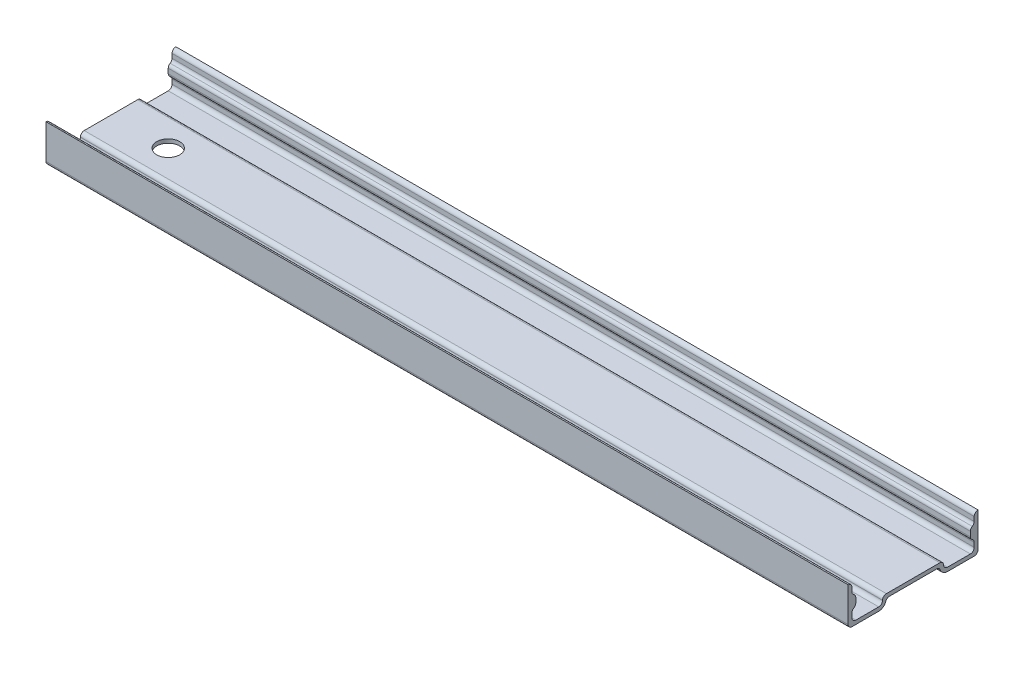
SolidWorks part; units mm, degrees
ref_plane "Front Plane" through (0, 0, 0) normal (0, 0, 1) x (1, 0, 0)
ref_plane "Top Plane" through (0, 0, 0) normal (0, 1, 0) x (1, 0, 0)
ref_plane "Right Plane" through (0, 0, 0) normal (1, 0, 0) x (0, 0, -1)
sketch "Sketch1" plane through (0, 0, 0) normal (0, 1, 0) x (1, 0, 0)
  line L0 (-105, 17) -> (105, -17) construction
  line L1 (-105, 17) -> (105, 17)
  line L2 (-105, 17) -> (-105, -17)
  line L3 (-105, -17) -> (105, -17)
  line L4 (105, 17) -> (105, -17)
  dimension "D1" = 34
  dimension "D2" = 210
extrude "Boss-Extrude1" add sketch "Sketch1" along normal blind 1
sketch "Sketch2" plane through (0, 1, 0) normal (0, 1, 0) x (1, 0, 0)
  line L0 (105, -17) -> (105, 17) construction
  line L1 (-105, 17) -> (105, 17)
  line L2 (-105, 17) -> (-105, 16)
  line L3 (-105, 16) -> (105, 16)
  line L4 (105, 17) -> (105, 16)
  line L6 (105, -16) -> (-105, -16)
  line L7 (105, -16) -> (105, -17)
  line L8 (105, -17) -> (-105, -17)
  line L9 (-105, -16) -> (-105, -17)
  dimension "D1" = 1
  dimension "D2" = 1
extrude "Boss-Extrude2" add sketch "Sketch2" along normal blind 9
sketch "Sketch3" plane through (0, 1, 0) normal (0, 1, 0) x (1, 0, 0)
  line L0 (-105, 16) -> (-105, -16) construction
  line L1 (-105, 8) -> (105, 8)
  line L2 (-105, 8) -> (-105, -8)
  line L3 (-105, -8) -> (105, -8)
  line L4 (105, 8) -> (105, -8)
  line L5 (105, -16) -> (105, 16) construction
  line L6 (-105, 8) -> (105, -8) construction
  dimension "D1" = 16
extrude "Boss-Extrude3" add sketch "Sketch3" along normal blind 2
fillet "Fillet1" radius 1 1 edges at (0, 1, 8) type face fillet first side face at (0, 2, 8) second side face at (0, 1, 12)
fillet "Fillet2" radius 1 1 edges at (0, 1, -8) type face fillet first side face at (0, 2, -8) second side face at (-26.25, 1, -12)
fillet "Fillet3" radius 1 1 edges at (0, 1, 16) type face fillet first side face at (0, 1, 12.5) second side face at (0, 5.5, 16)
fillet "Fillet4" radius 1 1 edges type face fillet first side face at (-26.25, 7.75, -16) second side face at (-26.25, 1, -12.5)
fillet "Fillet5" radius 1 1 edges at (0, 10, -16) type face fillet first side face at (0, 8, -16) second side face at (0, 10, -16.5)
fillet "Fillet6" radius 1 1 edges at (0, 10, 16) type face fillet first side face at (0, 6, 16) second side face at (0, 10, 16.5)
sketch "Sketch4" plane through (105, 0, 0) normal (1, 0, 0) x (0, 0, -1)
  line L0 (-9, 0) -> (9, 0)
  line L4 (-6.1716, 2) -> (6.1716, 2)
  arc A0 (-6.1716, 2) -> (-7.1144, 1.3333) centre (-6.1716, 1) ccw
  arc A1 (7.1144, 1.3333) -> (6.1716, 2) centre (6.1716, 1) ccw
  arc A2 (9, 0) -> (7.1144, 1.3333) centre (9, 2) cw
  arc A3 (-7.1144, 1.3333) -> (-9, 0) centre (-9, 2) cw
  dimension "D1" = 1
  dimension "D2" = 1
extrude "Cut-Extrude1" cut sketch "Sketch4" against normal through all
fillet "Fillet7" radius 1 1 edges at (0, 3, 8) type face fillet first side face at (0, 3, 0) second side face at (0, 2.5, 8)
fillet "Fillet8" radius 1 1 edges at (0, 3, -8) type face fillet first side face at (0, 3, -0.5) second side face at (0, 2.5, -8)
fillet "Fillet9" radius 1 1 edges at (0, 0, -17) type face fillet first side face at (0, 5, -17) second side face at (0, 0, -13)
fillet "Fillet10" radius 1 1 edges at (0, 0, 17) type face fillet first side face at (0, 5, 17) second side face at (0, 0, 13)
sketch "Sketch5" plane through (105, 0, 0) normal (1, 0, 0) x (0, 0, -1)
  line L0 (-15, 6.8718) -> (15, 6.8718) construction
  line L1 (-18, 6.8718) -> (-15, 6.8718)
  line L2 (-18, 6.8718) -> (-18, 3.8718)
  line L3 (-18, 3.8718) -> (-15, 3.8718)
  line L4 (-15, 6.8718) -> (-15, 3.8718)
  line L5 (15, 6.8718) -> (18, 6.8718)
  line L6 (15, 6.8718) -> (15, 3.8718)
  line L7 (15, 3.8718) -> (18, 3.8718)
  line L8 (18, 6.8718) -> (18, 3.8718)
  line L9 (-16, 9) -> (-16, 2) construction
  line L10 (16, 9) -> (16, 2) construction
  dimension "D1" = 1
  dimension "D2" = 1
  dimension "D3" = 3
extrude "Boss-Extrude4" add sketch "Sketch5" against normal blind 210
fillet "Fillet11" radius 1 1 edges at (0, 6.8718, 16) type face fillet first side face at (0, 7.9359, 16) second side face at (0, 6.8718, 15.5)
fillet "Fillet12" radius 1 1 edges at (0, 6.8718, 15) type face fillet first side face at (0, 5.3718, 15) second side face at (0, 7.2682, 15.6036)
fillet "Fillet13" radius 1 1 edges at (0, 3.8718, 15) type face fillet first side face at (0, 5.0057, 15) second side face at (0, 3.8718, 15.5)
fillet "Fillet14" radius 1 1 edges at (0, 3.8718, 16) type face fillet first side face at (0, 4.2682, 15.3964) second side face at (0, 2.9359, 16)
fillet "Fillet15" radius 1 1 edges at (0, 6.8718, -16) type face fillet first side face at (0, 8.4679, -16) second side face at (0, 6.8718, -15.5)
fillet "Fillet16" radius 1 1 edges at (0, 6.8718, -15) type face fillet first side face at (0, 7.2682, -15.6036) second side face at (0, 5.3718, -15)
fillet "Fillet17" radius 1 1 edges at (0, 3.8718, -15) type face fillet first side face at (0, 5.0057, -15) second side face at (0, 3.8718, -15.5)
fillet "Fillet18" radius 1 1 edges at (0, 3.8718, -16) type face fillet first side face at (0, 4.2682, -15.3964) second side face at (0, 3.4038, -16)
sketch "Sketch6" plane through (105, 0, 0) normal (1, 0, 0) x (0, 0, -1)
  line L0 (-18, 6.8718) -> (-18, 3.8718)
  line L1 (-18, 3.8718) -> (-17, 3.8718)
  line L2 (-17, 3.8718) -> (-17, 6.8718)
  line L3 (-17, 6.8718) -> (-18, 6.8718)
  line L4 (18, 6.8718) -> (17, 6.8718)
  line L5 (17, 6.8718) -> (17, 3.8718)
  line L6 (17, 3.8718) -> (18, 3.8718)
  line L7 (18, 3.8718) -> (18, 6.8718)
extrude "Cut-Extrude2" cut sketch "Sketch6" against normal blind 210
sketch "Sketch7" plane through (0, 2, 0) normal (0, -1, 0) x (1, 0, 0)
  line L0 (-105, -6.1716) -> (-105, 6.1716) construction
  circle A0 centre (-90, 0) radius 3
  dimension "D2" = 6
  dimension "D1" = 15
extrude "Cut-Extrude3" cut sketch "Sketch7" against normal blind 10
